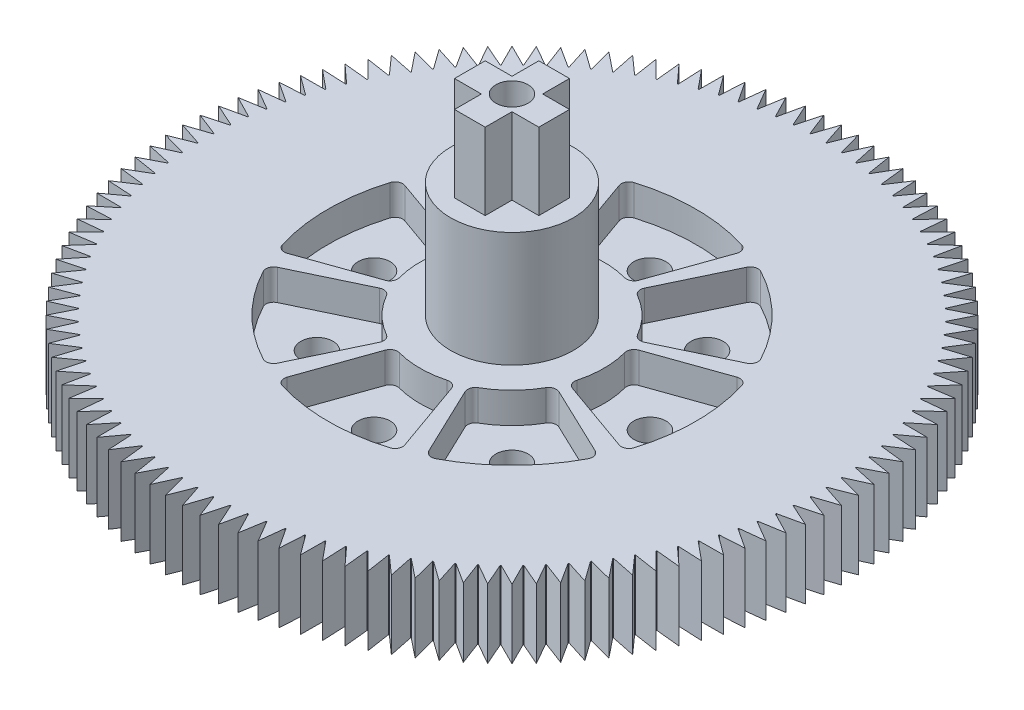
SolidWorks part; units mm, degrees
note: The reader was unsure of these and kept them because the rebuilt part matched: shared geometry of "Эскиз5<4>", "Эскиз5<5>", "Эскиз5<6>".
ref_plane "Спереди" through (0, 0, 0) normal (0, 0, 1) x (1, 0, 0)
ref_plane "Сверху" through (0, 0, 0) normal (0, 1, 0) x (1, 0, 0)
ref_plane "Справа" through (0, 0, 0) normal (1, 0, 0) x (0, 0, -1)
sketch "Эскиз1" plane through (0, 0, 0) normal (0, 1, 0) x (1, 0, 0)
  circle A1 centre (-18, 0) radius 2.1
  circle A2 centre (-12.7279, 12.7279) radius 2.1
  circle A3 centre (0, 18) radius 2.1
  circle A4 centre (12.7279, 12.7279) radius 2.1
  circle A5 centre (18, 0) radius 2.1
  circle A6 centre (12.7279, -12.7279) radius 2.1
  circle A7 centre (0, -18) radius 2.1
  circle A8 centre (-12.7279, -12.7279) radius 2.1
  circle A9 centre (0, 0) radius 25
extrude "Бобышка-Вытянуть1" add sketch "Эскиз1" along normal blind 5
ref_plane "Плоскость1" through (0, 5, 0) normal (0, 1, 0) x (1, 0, 0)
sketch "Эскиз2" plane through (0, 5, 0) normal (0, 1, 0) x (1, 0, 0)
  line L32 (-5.1661, -10.831) -> (-10.3323, -21.662)
  line L33 (-4.0057, -11.3117) -> (-8.0114, -22.6234)
  line L34 (-10.831, -5.1661) -> (-21.662, -10.3323)
  line L35 (-22.6234, -8.0114) -> (-11.3117, -4.0057)
  line L36 (-11.3117, 4.0057) -> (-22.6234, 8.0114)
  line L37 (-21.662, 10.3323) -> (-10.831, 5.1661)
  line L38 (-10.3323, 21.662) -> (-5.1661, 10.831)
  line L39 (-8.0114, 22.6234) -> (-4.0057, 11.3117)
  line L40 (8.0114, 22.6234) -> (4.0057, 11.3117)
  line L41 (10.3323, 21.662) -> (5.1661, 10.831)
  line L42 (10.831, 5.1661) -> (21.662, 10.3323)
  line L43 (11.3117, 4.0057) -> (22.6234, 8.0114)
  line L44 (11.3117, -4.0057) -> (22.6234, -8.0114)
  line L45 (10.831, -5.1661) -> (21.662, -10.3323)
  line L46 (5.1661, -10.831) -> (10.3323, -21.662)
  line L47 (4.0057, -11.3117) -> (8.0114, -22.6234)
  circle A1 centre (0, 0) radius 12
  circle A2 centre (0, 0) radius 25
  circle A4 centre (0, 0) radius 24
extrude "Бобышка-Вытянуть2" add sketch "Эскиз2" along normal blind 4 contours A2 A4 | A1 | L39 A4 L38 A1 | L41 A4 L40 A1 | L43 A4 L42 A1 | L45 A4 L44 A1 | L47 A4 L46 A1 | L32 A4 L33 A1 | L35 A4 L34 A1 | L37 A4 L36 A1
fillet "Скругление1" radius 1 32 edges at (-4.0057, 7, -11.3117) (4.0057, 7, -11.3117) (8.0114, 7, -22.6234) (-8.0114, 7, -22.6234) (21.662, 7, -10.3323) (10.3323, 7, -21.662) (5.1661, 7, -10.831) (10.831, 7, -5.1661) (22.6234, 7, -8.0114) (11.3117, 7, -4.0057) (11.3117, 7, 4.0057) (22.6234, 7, 8.0114) (21.662, 7, 10.3323) (10.831, 7, 5.1661) (5.1661, 7, 10.831) (10.3323, 7, 21.662) (8.0114, 7, 22.6234) (4.0057, 7, 11.3117) (-4.0057, 7, 11.3117) (-8.0114, 7, 22.6234) (-10.3323, 7, 21.662) (-5.1661, 7, 10.831) (-10.831, 7, 5.1661) (-21.662, 7, 10.3323) (-11.3117, 7, 4.0057) (-11.3117, 7, -4.0057) (-22.6234, 7, 8.0114) (-22.6234, 7, -8.0114) (-10.831, 7, -5.1661) (-5.1661, 7, -10.831) (-21.662, 7, -10.3323) (-10.3323, 7, -21.662)
ref_plane "Плоскость2" through (0, 9, 0) normal (0, 1, 0) x (1, 0, 0)
sketch "Эскиз3" plane through (0, 9, 0) normal (0, 1, 0) x (1, 0, 0)
  circle A0 centre (0, 0) radius 8
extrude "Бобышка-Вытянуть3" add sketch "Эскиз3" along normal blind 15
ref_plane "Плоскость3" through (0, 24, 0) normal (0, 1, 0) x (1, 0, 0)
sketch "Эскиз4" plane through (0, 24, 0) normal (0, 1, 0) x (1, 0, 0)
  line L4 (-2, -5.5) -> (-2, -2)
  line L5 (-5.5, 2) -> (-2, 2)
  line L11 (2, -5.5) -> (2, -2)
  line L12 (2, -2) -> (5.5, -2)
  line L13 (5.5, -2) -> (5.5, 2)
  line L14 (5.5, 2) -> (2, 2)
  line L15 (2, 2) -> (2, 5.5)
  line L16 (-2, 5.5) -> (2, 5.5)
  line L17 (-2, 5.5) -> (-2, 2)
  line L18 (-2, -2) -> (-5.5, -2)
  line L19 (-5.5, 2) -> (-5.5, -2)
  line L20 (-2, -5.5) -> (2, -5.5)
extrude "Бобышка-Вытянуть4" add sketch "Эскиз4" along normal blind 10
ref_plane "Плоскость4" through (0, 5, 0) normal (0, 1, 0) x (1, 0, 0)
sketch "Эскиз5" plane through (0, 5, 0) normal (0, 1, 0) x (1, 0, 0)
  line L7 (-0.9999, 39.9875) -> (0, 43)
  line L8 (1.0942, 39.985) -> (2.2504, 42.9411)
  line L9 (0.9999, 39.9875) -> (0, 43)
  line L10 (3.0913, 39.8804) -> (2.2504, 42.9411)
  line L11 (3.1854, 39.873) -> (4.4947, 42.7644)
  line L12 (5.1742, 39.6639) -> (4.4947, 42.7644)
  line L13 (5.2678, 39.6516) -> (6.7267, 42.4706)
  line L14 (7.243, 39.3388) -> (6.7267, 42.4706)
  line L15 (7.3358, 39.3216) -> (8.9402, 42.0603)
  line L16 (9.2919, 38.9058) -> (8.9402, 42.0603)
  line L17 (9.3837, 38.8838) -> (11.1292, 41.5348)
  line L18 (11.3153, 38.3662) -> (11.1292, 41.5348)
  line L19 (11.4058, 38.3394) -> (13.2877, 40.8954)
  line L20 (13.3077, 37.7214) -> (13.2877, 40.8954)
  line L21 (13.3967, 37.6899) -> (15.4098, 40.144)
  line L22 (15.2637, 36.9732) -> (15.4098, 40.144)
  line L23 (15.3509, 36.9371) -> (17.4897, 39.2825)
  line L24 (17.1778, 36.1237) -> (17.4897, 39.2825)
  line L25 (17.263, 36.0831) -> (19.5216, 38.3133)
  line L26 (19.0448, 35.1752) -> (19.5216, 38.3133)
  line L27 (19.1278, 35.1302) -> (21.5, 37.2391)
  line L28 (20.8597, 34.1303) -> (21.5, 37.2391)
  line L29 (20.9401, 34.0809) -> (23.4195, 36.0628)
  line L30 (22.6173, 32.9918) -> (23.4195, 36.0628)
  line L31 (22.6951, 32.9383) -> (25.2748, 34.7877)
  line L32 (24.313, 31.7629) -> (25.2748, 34.7877)
  line L33 (24.3879, 31.7054) -> (27.0608, 33.4173)
  line L34 (25.942, 30.4469) -> (27.0608, 33.4173)
  line L35 (26.0138, 30.3856) -> (28.7726, 31.9552)
  line L36 (27.4999, 29.0475) -> (28.7726, 31.9552)
  line L37 (27.5684, 28.9825) -> (30.4056, 30.4056)
  line L38 (28.9824, 27.5684) -> (30.4056, 30.4056)
  line L39 (29.0474, 27.4999) -> (31.9552, 28.7726)
  line L40 (30.3855, 26.0138) -> (31.9552, 28.7726)
  line L41 (30.4469, 25.942) -> (33.4173, 27.0608)
  line L42 (31.7054, 24.3879) -> (33.4173, 27.0608)
  line L43 (31.7628, 24.313) -> (34.7877, 25.2748)
  line L44 (32.9383, 22.6952) -> (34.7877, 25.2748)
  line L45 (32.9917, 22.6174) -> (36.0628, 23.4195)
  line L46 (34.0809, 20.9402) -> (36.0628, 23.4195)
  line L47 (34.1302, 20.8597) -> (37.2391, 21.5)
  line L48 (35.1301, 19.1278) -> (37.2391, 21.5)
  line L49 (35.1752, 19.0449) -> (38.3133, 19.5216)
  line L50 (36.0831, 17.2631) -> (38.3133, 19.5216)
  line L51 (36.1237, 17.1779) -> (39.2825, 17.4897)
  line L52 (36.9371, 15.351) -> (39.2825, 17.4897)
  line L53 (36.9732, 15.2637) -> (40.144, 15.4098)
  line L54 (37.6899, 13.3968) -> (40.144, 15.4098)
  line L55 (37.7214, 13.3078) -> (40.8954, 13.2877)
  line L56 (38.3393, 11.4059) -> (40.8954, 13.2877)
  line L57 (38.3662, 11.3154) -> (41.5348, 11.1292)
  line L58 (38.8837, 9.3837) -> (41.5348, 11.1292)
  line L59 (38.9058, 9.2919) -> (42.0603, 8.9402)
  line L60 (39.3216, 7.3359) -> (42.0603, 8.9402)
  line L61 (39.3388, 7.243) -> (42.4706, 6.7267)
  line L62 (39.6516, 5.2679) -> (42.4706, 6.7267)
  line L63 (39.6639, 5.1743) -> (42.7644, 4.4947)
  line L64 (39.873, 3.1854) -> (42.7644, 4.4947)
  line L65 (39.8804, 3.0913) -> (42.9411, 2.2504)
  line L66 (39.985, 1.0943) -> (42.9411, 2.2504)
  line L67 (39.9875, 0.9999) -> (43, 0)
  line L68 (39.9875, -0.9999) -> (43, 0)
  line L69 (39.985, -1.0942) -> (42.9411, -2.2504)
  line L70 (39.8804, -3.0913) -> (42.9411, -2.2504)
  line L71 (39.873, -3.1854) -> (42.7644, -4.4947)
  line L72 (39.6639, -5.1742) -> (42.7644, -4.4947)
  line L73 (39.6516, -5.2678) -> (42.4706, -6.7267)
  line L74 (39.3388, -7.243) -> (42.4706, -6.7267)
  line L75 (39.3216, -7.3358) -> (42.0603, -8.9402)
  line L76 (38.9058, -9.2919) -> (42.0603, -8.9402)
  line L77 (38.8838, -9.3837) -> (41.5348, -11.1292)
  line L78 (38.3662, -11.3153) -> (41.5348, -11.1292)
  line L79 (38.3394, -11.4058) -> (40.8954, -13.2877)
  line L80 (37.7214, -13.3077) -> (40.8954, -13.2877)
  line L81 (37.6899, -13.3967) -> (40.144, -15.4098)
  line L82 (36.9732, -15.2637) -> (40.144, -15.4098)
  line L83 (36.9371, -15.3509) -> (39.2825, -17.4897)
  line L84 (36.1237, -17.1778) -> (39.2825, -17.4897)
  line L85 (36.0831, -17.263) -> (38.3133, -19.5216)
  line L86 (35.1752, -19.0448) -> (38.3133, -19.5216)
  line L87 (35.1302, -19.1278) -> (37.2391, -21.5)
  line L88 (34.1303, -20.8597) -> (37.2391, -21.5)
  line L89 (34.0809, -20.9401) -> (36.0628, -23.4195)
  line L90 (32.9918, -22.6173) -> (36.0628, -23.4195)
  line L91 (32.9383, -22.6951) -> (34.7877, -25.2748)
  line L92 (31.7629, -24.313) -> (34.7877, -25.2748)
  line L93 (-0.9999, -29.9833) -> (0, -33)
  line L94 (0.9999, -29.9833) -> (0, -33)
  line L95 (31.7054, -24.3879) -> (33.4173, -27.0608)
  line L96 (30.4469, -25.942) -> (33.4173, -27.0608)
  line L97 (30.3856, -26.0138) -> (31.9552, -28.7726)
  line L98 (29.0475, -27.4999) -> (31.9552, -28.7726)
  line L99 (28.9825, -27.5684) -> (30.4056, -30.4056)
  line L100 (27.5684, -28.9824) -> (30.4056, -30.4056)
  line L101 (27.4999, -29.0474) -> (28.7726, -31.9552)
  line L102 (26.0138, -30.3855) -> (28.7726, -31.9552)
  line L103 (25.942, -30.4469) -> (27.0608, -33.4173)
  line L104 (24.3879, -31.7054) -> (27.0608, -33.4173)
  line L105 (24.313, -31.7628) -> (25.2748, -34.7877)
  line L106 (22.6952, -32.9383) -> (25.2748, -34.7877)
  line L107 (22.6174, -32.9917) -> (23.4195, -36.0628)
  line L108 (20.9402, -34.0809) -> (23.4195, -36.0628)
  line L109 (20.8597, -34.1302) -> (21.5, -37.2391)
  line L110 (19.1278, -35.1301) -> (21.5, -37.2391)
  line L111 (19.0449, -35.1752) -> (19.5216, -38.3133)
  line L112 (17.2631, -36.0831) -> (19.5216, -38.3133)
  line L113 (17.1779, -36.1237) -> (17.4897, -39.2825)
  line L114 (15.351, -36.9371) -> (17.4897, -39.2825)
  line L115 (15.2637, -36.9732) -> (15.4098, -40.144)
  line L116 (13.3968, -37.6899) -> (15.4098, -40.144)
  line L117 (13.3078, -37.7214) -> (13.2877, -40.8954)
  line L118 (11.4059, -38.3393) -> (13.2877, -40.8954)
  line L119 (11.3154, -38.3662) -> (11.1292, -41.5348)
  line L120 (9.3837, -38.8837) -> (11.1292, -41.5348)
  line L121 (9.2919, -38.9058) -> (8.9402, -42.0603)
  line L122 (7.3359, -39.3216) -> (8.9402, -42.0603)
  line L123 (7.243, -39.3388) -> (6.7267, -42.4706)
  line L124 (5.2679, -39.6516) -> (6.7267, -42.4706)
  line L125 (5.1743, -39.6639) -> (4.4947, -42.7644)
  line L126 (3.1854, -39.873) -> (4.4947, -42.7644)
  line L127 (3.0913, -39.8804) -> (2.2504, -42.9411)
  line L128 (1.0943, -39.985) -> (2.2504, -42.9411)
  line L129 (0.9999, -39.9875) -> (0, -43)
  line L130 (-0.9999, -39.9875) -> (0, -43)
  line L131 (-1.0942, -39.985) -> (-2.2504, -42.9411)
  line L132 (-3.0913, -39.8804) -> (-2.2504, -42.9411)
  line L133 (-3.1854, -39.873) -> (-4.4947, -42.7644)
  line L134 (-5.1742, -39.6639) -> (-4.4947, -42.7644)
  line L135 (-5.2678, -39.6516) -> (-6.7267, -42.4706)
  line L136 (-7.243, -39.3388) -> (-6.7267, -42.4706)
  line L137 (-7.3358, -39.3216) -> (-8.9402, -42.0603)
  line L138 (-9.2919, -38.9058) -> (-8.9402, -42.0603)
  line L139 (-9.3837, -38.8838) -> (-11.1292, -41.5348)
  line L140 (-11.3153, -38.3662) -> (-11.1292, -41.5348)
  line L141 (-11.4058, -38.3394) -> (-13.2877, -40.8954)
  line L142 (-13.3077, -37.7214) -> (-13.2877, -40.8954)
  line L143 (-13.3967, -37.6899) -> (-15.4098, -40.144)
  line L144 (-15.2637, -36.9732) -> (-15.4098, -40.144)
  line L145 (-15.3509, -36.9371) -> (-17.4897, -39.2825)
  line L146 (-17.1778, -36.1237) -> (-17.4897, -39.2825)
  line L147 (-17.263, -36.0831) -> (-19.5216, -38.3133)
  line L148 (-19.0448, -35.1752) -> (-19.5216, -38.3133)
  line L149 (-19.1278, -35.1302) -> (-21.5, -37.2391)
  line L150 (-20.8597, -34.1303) -> (-21.5, -37.2391)
  line L151 (-20.9401, -34.0809) -> (-23.4195, -36.0628)
  line L152 (-22.6173, -32.9918) -> (-23.4195, -36.0628)
  line L153 (-22.6951, -32.9383) -> (-25.2748, -34.7877)
  line L154 (-24.313, -31.7629) -> (-25.2748, -34.7877)
  line L155 (-24.3879, -31.7054) -> (-27.0608, -33.4173)
  line L156 (-25.942, -30.4469) -> (-27.0608, -33.4173)
  line L157 (-26.0138, -30.3856) -> (-28.7726, -31.9552)
  line L158 (-27.4999, -29.0475) -> (-28.7726, -31.9552)
  line L159 (-27.5684, -28.9825) -> (-30.4056, -30.4056)
  line L160 (-28.9824, -27.5684) -> (-30.4056, -30.4056)
  line L161 (-29.0474, -27.4999) -> (-31.9552, -28.7726)
  line L162 (-30.3855, -26.0138) -> (-31.9552, -28.7726)
  line L163 (-30.4469, -25.942) -> (-33.4173, -27.0608)
  line L164 (-31.7054, -24.3879) -> (-33.4173, -27.0608)
  line L165 (-31.7628, -24.313) -> (-34.7877, -25.2748)
  line L166 (-32.9383, -22.6952) -> (-34.7877, -25.2748)
  line L167 (-32.9917, -22.6174) -> (-36.0628, -23.4195)
  line L168 (-34.0809, -20.9402) -> (-36.0628, -23.4195)
  line L169 (-34.1302, -20.8597) -> (-37.2391, -21.5)
  line L170 (-35.1301, -19.1278) -> (-37.2391, -21.5)
  line L171 (-35.1752, -19.0449) -> (-38.3133, -19.5216)
  line L172 (-36.0831, -17.2631) -> (-38.3133, -19.5216)
  line L173 (-36.1237, -17.1779) -> (-39.2825, -17.4897)
  line L174 (-36.9371, -15.351) -> (-39.2825, -17.4897)
  line L175 (-36.9732, -15.2637) -> (-40.144, -15.4098)
  line L176 (-37.6899, -13.3968) -> (-40.144, -15.4098)
  line L177 (-37.7214, -13.3078) -> (-40.8954, -13.2877)
  line L178 (-38.3393, -11.4059) -> (-40.8954, -13.2877)
  line L179 (-38.3662, -11.3154) -> (-41.5348, -11.1292)
  line L180 (-38.8837, -9.3837) -> (-41.5348, -11.1292)
  line L181 (-38.9058, -9.2919) -> (-42.0603, -8.9402)
  line L182 (-39.3216, -7.3359) -> (-42.0603, -8.9402)
  line L359 (-39.3388, -7.243) -> (-42.4706, -6.7267)
  line L360 (-39.6516, -5.2679) -> (-42.4706, -6.7267)
  line L361 (-39.6639, -5.1743) -> (-42.7644, -4.4947)
  line L362 (-39.873, -3.1854) -> (-42.7644, -4.4947)
  line L363 (-39.8804, -3.0913) -> (-42.9411, -2.2504)
  line L364 (-39.985, -1.0943) -> (-42.9411, -2.2504)
  line L365 (-39.9875, -0.9999) -> (-43, 0)
  line L366 (-39.9875, 0.9999) -> (-43, 0)
  line L367 (-39.985, 1.0942) -> (-42.9411, 2.2504)
  line L368 (-39.8804, 3.0913) -> (-42.9411, 2.2504)
  line L369 (-39.873, 3.1854) -> (-42.7644, 4.4947)
  line L370 (-39.6639, 5.1742) -> (-42.7644, 4.4947)
  line L371 (-39.6516, 5.2678) -> (-42.4706, 6.7267)
  line L372 (-39.3388, 7.243) -> (-42.4706, 6.7267)
  line L373 (-39.3216, 7.3358) -> (-42.0603, 8.9402)
  line L374 (-38.9058, 9.2919) -> (-42.0603, 8.9402)
  line L375 (-38.8838, 9.3837) -> (-41.5348, 11.1292)
  line L376 (-38.3662, 11.3153) -> (-41.5348, 11.1292)
  line L377 (-38.3394, 11.4058) -> (-40.8954, 13.2877)
  line L378 (-37.7214, 13.3077) -> (-40.8954, 13.2877)
  line L379 (-37.6899, 13.3967) -> (-40.144, 15.4098)
  line L380 (-36.9732, 15.2637) -> (-40.144, 15.4098)
  line L381 (-36.9371, 15.3509) -> (-39.2825, 17.4897)
  line L382 (-36.1237, 17.1778) -> (-39.2825, 17.4897)
  line L383 (-36.0831, 17.263) -> (-38.3133, 19.5216)
  line L384 (-35.1752, 19.0448) -> (-38.3133, 19.5216)
  line L385 (-35.1302, 19.1278) -> (-37.2391, 21.5)
  line L386 (-34.1303, 20.8597) -> (-37.2391, 21.5)
  line L387 (-34.0809, 20.9401) -> (-36.0628, 23.4195)
  line L388 (-32.9918, 22.6173) -> (-36.0628, 23.4195)
  line L389 (-32.9383, 22.6951) -> (-34.7877, 25.2748)
  line L390 (-31.7629, 24.313) -> (-34.7877, 25.2748)
  line L391 (-31.7054, 24.3879) -> (-33.4173, 27.0608)
  line L392 (-30.4469, 25.942) -> (-33.4173, 27.0608)
  line L393 (-30.3856, 26.0138) -> (-31.9552, 28.7726)
  line L394 (-29.0475, 27.4999) -> (-31.9552, 28.7726)
  line L395 (-28.9825, 27.5684) -> (-30.4056, 30.4056)
  line L396 (-27.5684, 28.9824) -> (-30.4056, 30.4056)
  line L397 (-27.4999, 29.0474) -> (-28.7726, 31.9552)
  line L398 (-26.0138, 30.3855) -> (-28.7726, 31.9552)
  line L399 (-25.942, 30.4469) -> (-27.0608, 33.4173)
  line L400 (-24.3879, 31.7054) -> (-27.0608, 33.4173)
  line L401 (-24.313, 31.7628) -> (-25.2748, 34.7877)
  line L402 (-22.6952, 32.9383) -> (-25.2748, 34.7877)
  line L403 (-22.6174, 32.9917) -> (-23.4195, 36.0628)
  line L404 (-20.9402, 34.0809) -> (-23.4195, 36.0628)
  line L405 (-20.8597, 34.1302) -> (-21.5, 37.2391)
  line L406 (-19.1278, 35.1301) -> (-21.5, 37.2391)
  line L407 (-19.0449, 35.1752) -> (-19.5216, 38.3133)
  line L408 (-17.2631, 36.0831) -> (-19.5216, 38.3133)
  line L409 (-17.1779, 36.1237) -> (-17.4897, 39.2825)
  line L410 (-15.351, 36.9371) -> (-17.4897, 39.2825)
  line L411 (-15.2637, 36.9732) -> (-15.4098, 40.144)
  line L412 (-13.3968, 37.6899) -> (-15.4098, 40.144)
  line L413 (-13.3078, 37.7214) -> (-13.2877, 40.8954)
  line L414 (-11.4059, 38.3393) -> (-13.2877, 40.8954)
  line L415 (-11.3154, 38.3662) -> (-11.1292, 41.5348)
  line L416 (-9.3837, 38.8837) -> (-11.1292, 41.5348)
  line L417 (-9.2919, 38.9058) -> (-8.9402, 42.0603)
  line L418 (-7.3359, 39.3216) -> (-8.9402, 42.0603)
  line L419 (-7.243, 39.3388) -> (-6.7267, 42.4706)
  line L420 (-5.2679, 39.6516) -> (-6.7267, 42.4706)
  line L421 (-5.1743, 39.6639) -> (-4.4947, 42.7644)
  line L422 (-3.1854, 39.873) -> (-4.4947, 42.7644)
  line L423 (-3.0913, 39.8804) -> (-2.2504, 42.9411)
  line L424 (-1.0943, 39.985) -> (-2.2504, 42.9411)
  circle A0 centre (0, 0) radius 25
  circle A1 centre (0, 0) radius 40
  point P277 (0, 0)
  point P722 (0, 0)
extrude "Бобышка-Вытянуть5" add sketch "Эскиз5" along normal blind 4 and the other way blind 5
extrude "Бобышка-Вытянуть6" add sketch "Эскиз5<4>" against normal blind 5 and the other way blind 4
sketch "Эскиз5<4>" plane through (0, 5, 0) normal (0, 1, 0) x (1, 0, 0) same geometry as "Эскиз5"
extrude "Бобышка-Вытянуть7" add sketch "Эскиз5<5>" against normal blind 5 and the other way blind 4
sketch "Эскиз5<5>" plane through (0, 5, 0) normal (0, 1, 0) x (1, 0, 0) same geometry as "Эскиз5"
extrude "Бобышка-Вытянуть8" add sketch "Эскиз5<6>" along normal blind 4 and the other way blind 5 contours A1 L414 L413 | A1 L422 L421 | A1 L12 L11 | A1 L20 L19 | A1 L28 L27 | A1 L36 L35 | A1 L44 L43 | A1 L52 L51 | A1 L60 L59 | A1 L68 L67 | A1 L76 L75 | A1 L84 L83 | A1 L92 L91 | A1 L102 L101 | A1 L110 L109 | A1 L118 L117 | A1 L126 L125 | A1 L134 L133 | A1 L142 L141 | A1 L150 L149 | A1 L158 L157 | A1 L166 L165 | A1 L174 L173 | A1 L182 L181 | A1 L366 L365 | A1 L374 L373 | A1 L382 L381 | A1 L390 L389 | A1 L398 L397 | A1 L406 L405
sketch "Эскиз5<6>" plane through (0, 5, 0) normal (0, 1, 0) x (1, 0, 0) same geometry as "Эскиз5"
ref_plane "Плоскость5" through (0, 34, 0) normal (0, 1, 0) x (1, 0, 0)
sketch "Эскиз6" plane through (0, 34, 0) normal (0, 1, 0) x (1, 0, 0)
  circle A0 centre (0, 0) radius 2.1
extrude "Вырез-Вытянуть1" cut sketch "Эскиз6" against normal through all both and the other way through all
